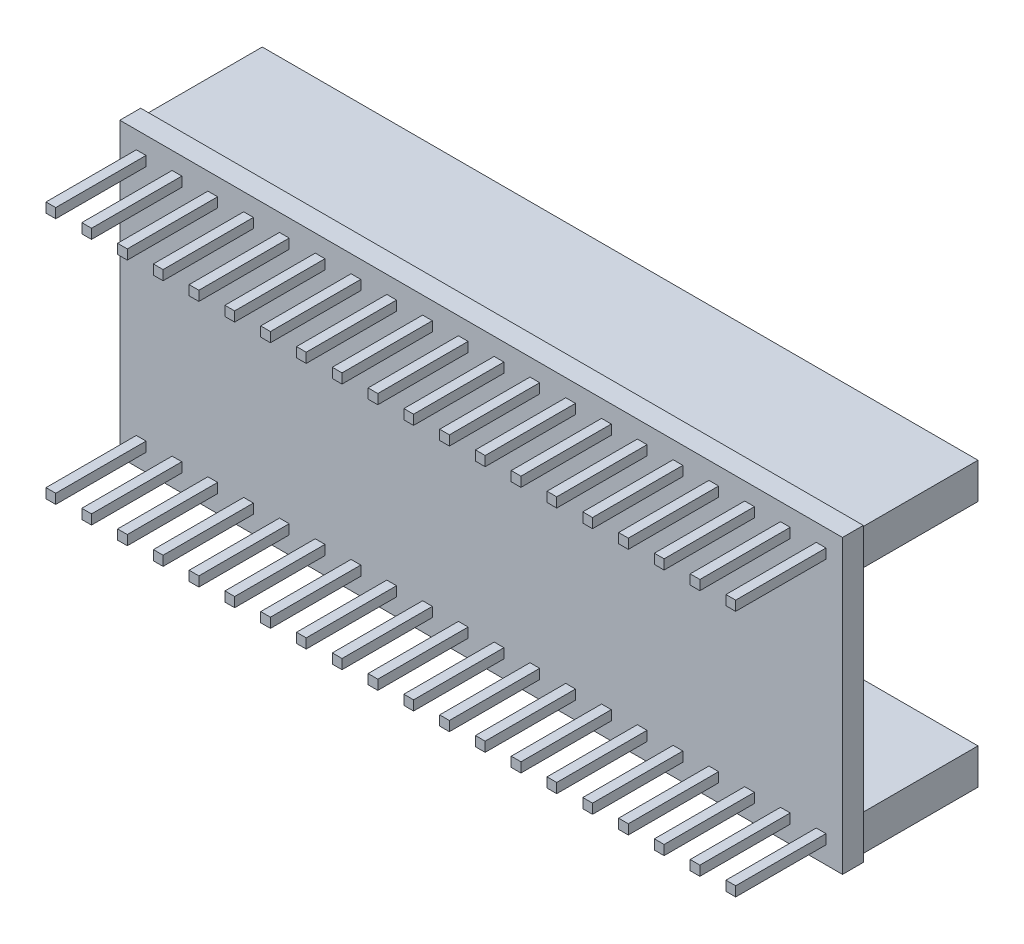
SolidWorks part; units mm, degrees
ref_plane "Спереди" through (0, 0, 0) normal (0, 0, 1) x (1, 0, 0)
ref_plane "Сверху" through (0, 0, 0) normal (0, 1, 0) x (1, 0, 0)
ref_plane "Справа" through (0, 0, 0) normal (1, 0, 0) x (0, 0, -1)
sketch "Эскиз1" plane through (0, 0, 0) normal (0, 0, 1) x (1, 0, 0)
  line L0 (-56.9339, 10.5) -> (3.8181, 10.5) construction
  line L1 (0, 0) -> (-52, 0)
  line L2 (0, 0) -> (0, 21)
  line L3 (0, 21) -> (-52, 21)
  line L4 (-52, 0) -> (-52, 21)
  line L5 (-26, 25.408) -> (-26, -2.6209) construction
  line L6 (-51.75, 18.1125) -> (-0.25, 18.1125)
  line L7 (-51.75, 18.1125) -> (-51.75, 20.6875)
  line L8 (-51.75, 20.6875) -> (-0.25, 20.6875)
  line L9 (-0.25, 18.1125) -> (-0.25, 20.6875)
  line L10 (-0.25, 2.8875) -> (-0.25, 0.3125)
  line L11 (-51.75, 0.3125) -> (-0.25, 0.3125)
  line L12 (-51.75, 2.8875) -> (-0.25, 2.8875)
  line L13 (-51.75, 2.8875) -> (-51.75, 0.3125)
  line L14 (-49.175, 20.6875) -> (-49.175, 18.1125) construction
  line L15 (-50.4625, 20.8345) -> (-50.4625, 17.8759) construction
  line L16 (-51.907, 19.4) -> (-48.9961, 19.4) construction
  line L17 (-48.2375, 19.05) -> (-48.2375, 19.75)
  line L18 (-50.8125, 19.05) -> (-50.1125, 19.05)
  line L19 (-50.8125, 19.05) -> (-50.8125, 19.75)
  line L20 (-50.8125, 19.75) -> (-50.1125, 19.75)
  line L21 (-50.1125, 19.05) -> (-50.1125, 19.75)
  line L22 (-50.8125, 19.05) -> (-50.1125, 19.75) construction
  line L23 (-50.8125, 19.75) -> (-50.1125, 19.05) construction
  line L24 (-48.2375, 19.05) -> (-47.5375, 19.05)
  line L25 (-47.5375, 19.05) -> (-47.5375, 19.75)
  line L26 (-48.2375, 19.75) -> (-47.5375, 19.75)
  line L27 (-48.2375, 19.75) -> (-47.5375, 19.05) construction
  line L28 (-48.2375, 19.05) -> (-47.5375, 19.75) construction
  line L29 (-45.6625, 19.05) -> (-45.6625, 19.75)
  line L30 (-45.6625, 19.05) -> (-44.9625, 19.05)
  line L31 (-44.9625, 19.05) -> (-44.9625, 19.75)
  line L32 (-45.6625, 19.75) -> (-44.9625, 19.75)
  line L33 (-45.6625, 19.75) -> (-44.9625, 19.05) construction
  line L34 (-45.6625, 19.05) -> (-44.9625, 19.75) construction
  line L35 (-43.0875, 19.05) -> (-43.0875, 19.75)
  line L36 (-43.0875, 19.05) -> (-42.3875, 19.05)
  line L37 (-42.3875, 19.05) -> (-42.3875, 19.75)
  line L38 (-43.0875, 19.75) -> (-42.3875, 19.75)
  line L39 (-43.0875, 19.75) -> (-42.3875, 19.05) construction
  line L40 (-43.0875, 19.05) -> (-42.3875, 19.75) construction
  line L41 (-40.5125, 19.05) -> (-40.5125, 19.75)
  line L42 (-40.5125, 19.05) -> (-39.8125, 19.05)
  line L43 (-39.8125, 19.05) -> (-39.8125, 19.75)
  line L44 (-40.5125, 19.75) -> (-39.8125, 19.75)
  line L45 (-40.5125, 19.75) -> (-39.8125, 19.05) construction
  line L46 (-40.5125, 19.05) -> (-39.8125, 19.75) construction
  line L47 (-37.9375, 19.05) -> (-37.9375, 19.75)
  line L48 (-37.9375, 19.05) -> (-37.2375, 19.05)
  line L49 (-37.2375, 19.05) -> (-37.2375, 19.75)
  line L50 (-37.9375, 19.75) -> (-37.2375, 19.75)
  line L51 (-37.9375, 19.75) -> (-37.2375, 19.05) construction
  line L52 (-37.9375, 19.05) -> (-37.2375, 19.75) construction
  line L53 (-35.3625, 19.05) -> (-35.3625, 19.75)
  line L54 (-35.3625, 19.05) -> (-34.6625, 19.05)
  line L55 (-34.6625, 19.05) -> (-34.6625, 19.75)
  line L56 (-35.3625, 19.75) -> (-34.6625, 19.75)
  line L57 (-35.3625, 19.75) -> (-34.6625, 19.05) construction
  line L58 (-35.3625, 19.05) -> (-34.6625, 19.75) construction
  line L59 (-32.7875, 19.05) -> (-32.7875, 19.75)
  line L60 (-32.7875, 19.05) -> (-32.0875, 19.05)
  line L61 (-32.0875, 19.05) -> (-32.0875, 19.75)
  line L62 (-32.7875, 19.75) -> (-32.0875, 19.75)
  line L63 (-32.7875, 19.75) -> (-32.0875, 19.05) construction
  line L64 (-32.7875, 19.05) -> (-32.0875, 19.75) construction
  line L65 (-30.2125, 19.05) -> (-30.2125, 19.75)
  line L66 (-30.2125, 19.05) -> (-29.5125, 19.05)
  line L67 (-29.5125, 19.05) -> (-29.5125, 19.75)
  line L68 (-30.2125, 19.75) -> (-29.5125, 19.75)
  line L69 (-30.2125, 19.75) -> (-29.5125, 19.05) construction
  line L70 (-30.2125, 19.05) -> (-29.5125, 19.75) construction
  line L71 (-27.6375, 19.05) -> (-27.6375, 19.75)
  line L72 (-27.6375, 19.05) -> (-26.9375, 19.05)
  line L73 (-26.9375, 19.05) -> (-26.9375, 19.75)
  line L74 (-27.6375, 19.75) -> (-26.9375, 19.75)
  line L75 (-27.6375, 19.75) -> (-26.9375, 19.05) construction
  line L76 (-27.6375, 19.05) -> (-26.9375, 19.75) construction
  line L77 (-25.0625, 19.05) -> (-25.0625, 19.75)
  line L78 (-25.0625, 19.05) -> (-24.3625, 19.05)
  line L79 (-24.3625, 19.05) -> (-24.3625, 19.75)
  line L80 (-25.0625, 19.75) -> (-24.3625, 19.75)
  line L81 (-25.0625, 19.75) -> (-24.3625, 19.05) construction
  line L82 (-25.0625, 19.05) -> (-24.3625, 19.75) construction
  line L83 (-22.4875, 19.05) -> (-22.4875, 19.75)
  line L84 (-22.4875, 19.05) -> (-21.7875, 19.05)
  line L85 (-21.7875, 19.05) -> (-21.7875, 19.75)
  line L86 (-22.4875, 19.75) -> (-21.7875, 19.75)
  line L87 (-22.4875, 19.75) -> (-21.7875, 19.05) construction
  line L88 (-22.4875, 19.05) -> (-21.7875, 19.75) construction
  line L89 (-19.9125, 19.05) -> (-19.9125, 19.75)
  line L90 (-19.9125, 19.05) -> (-19.2125, 19.05)
  line L91 (-19.2125, 19.05) -> (-19.2125, 19.75)
  line L92 (-19.9125, 19.75) -> (-19.2125, 19.75)
  line L93 (-19.9125, 19.75) -> (-19.2125, 19.05) construction
  line L94 (-19.9125, 19.05) -> (-19.2125, 19.75) construction
  line L95 (-17.3375, 19.05) -> (-17.3375, 19.75)
  line L96 (-17.3375, 19.05) -> (-16.6375, 19.05)
  line L97 (-16.6375, 19.05) -> (-16.6375, 19.75)
  line L98 (-17.3375, 19.75) -> (-16.6375, 19.75)
  line L99 (-17.3375, 19.75) -> (-16.6375, 19.05) construction
  line L100 (-17.3375, 19.05) -> (-16.6375, 19.75) construction
  line L101 (-14.7625, 19.05) -> (-14.7625, 19.75)
  line L102 (-14.7625, 19.05) -> (-14.0625, 19.05)
  line L103 (-14.0625, 19.05) -> (-14.0625, 19.75)
  line L104 (-14.7625, 19.75) -> (-14.0625, 19.75)
  line L105 (-14.7625, 19.75) -> (-14.0625, 19.05) construction
  line L106 (-14.7625, 19.05) -> (-14.0625, 19.75) construction
  line L107 (-12.1875, 19.05) -> (-12.1875, 19.75)
  line L108 (-12.1875, 19.05) -> (-11.4875, 19.05)
  line L109 (-11.4875, 19.05) -> (-11.4875, 19.75)
  line L110 (-12.1875, 19.75) -> (-11.4875, 19.75)
  line L111 (-12.1875, 19.75) -> (-11.4875, 19.05) construction
  line L112 (-12.1875, 19.05) -> (-11.4875, 19.75) construction
  line L113 (-9.6125, 19.05) -> (-9.6125, 19.75)
  line L114 (-9.6125, 19.05) -> (-8.9125, 19.05)
  line L115 (-8.9125, 19.05) -> (-8.9125, 19.75)
  line L116 (-9.6125, 19.75) -> (-8.9125, 19.75)
  line L117 (-9.6125, 19.75) -> (-8.9125, 19.05) construction
  line L118 (-9.6125, 19.05) -> (-8.9125, 19.75) construction
  line L119 (-7.0375, 19.05) -> (-7.0375, 19.75)
  line L120 (-7.0375, 19.05) -> (-6.3375, 19.05)
  line L121 (-6.3375, 19.05) -> (-6.3375, 19.75)
  line L122 (-7.0375, 19.75) -> (-6.3375, 19.75)
  line L123 (-7.0375, 19.75) -> (-6.3375, 19.05) construction
  line L124 (-7.0375, 19.05) -> (-6.3375, 19.75) construction
  line L125 (-4.4625, 19.05) -> (-4.4625, 19.75)
  line L126 (-4.4625, 19.05) -> (-3.7625, 19.05)
  line L127 (-3.7625, 19.05) -> (-3.7625, 19.75)
  line L128 (-4.4625, 19.75) -> (-3.7625, 19.75)
  line L129 (-4.4625, 19.75) -> (-3.7625, 19.05) construction
  line L130 (-4.4625, 19.05) -> (-3.7625, 19.75) construction
  line L131 (-1.8875, 19.05) -> (-1.8875, 19.75)
  line L132 (-1.8875, 19.05) -> (-1.1875, 19.05)
  line L133 (-1.1875, 19.05) -> (-1.1875, 19.75)
  line L134 (-1.8875, 19.75) -> (-1.1875, 19.75)
  line L135 (-1.8875, 19.75) -> (-1.1875, 19.05) construction
  line L136 (-1.8875, 19.05) -> (-1.1875, 19.75) construction
  line L137 (-50.8125, 1.95) -> (-50.1125, 1.25) construction
  line L138 (-50.8125, 1.25) -> (-50.1125, 1.95) construction
  line L139 (-50.8125, 1.25) -> (-50.1125, 1.25)
  line L140 (-50.1125, 1.95) -> (-50.1125, 1.25)
  line L141 (-50.8125, 1.95) -> (-50.1125, 1.95)
  line L142 (-50.8125, 1.95) -> (-50.8125, 1.25)
  line L143 (-48.2375, 1.25) -> (-47.5375, 1.25)
  line L144 (-47.5375, 1.95) -> (-47.5375, 1.25)
  line L145 (-48.2375, 1.95) -> (-47.5375, 1.95)
  line L146 (-48.2375, 1.95) -> (-48.2375, 1.25)
  line L147 (-48.2375, 1.95) -> (-47.5375, 1.25) construction
  line L148 (-48.2375, 1.25) -> (-47.5375, 1.95) construction
  line L149 (-45.6625, 1.25) -> (-44.9625, 1.25)
  line L150 (-44.9625, 1.95) -> (-44.9625, 1.25)
  line L151 (-45.6625, 1.95) -> (-44.9625, 1.95)
  line L152 (-45.6625, 1.95) -> (-45.6625, 1.25)
  line L153 (-45.6625, 1.95) -> (-44.9625, 1.25) construction
  line L154 (-45.6625, 1.25) -> (-44.9625, 1.95) construction
  line L155 (-43.0875, 1.25) -> (-42.3875, 1.25)
  line L156 (-42.3875, 1.95) -> (-42.3875, 1.25)
  line L157 (-43.0875, 1.95) -> (-42.3875, 1.95)
  line L158 (-43.0875, 1.95) -> (-43.0875, 1.25)
  line L159 (-43.0875, 1.95) -> (-42.3875, 1.25) construction
  line L160 (-43.0875, 1.25) -> (-42.3875, 1.95) construction
  line L161 (-40.5125, 1.25) -> (-39.8125, 1.25)
  line L162 (-39.8125, 1.95) -> (-39.8125, 1.25)
  line L163 (-40.5125, 1.95) -> (-39.8125, 1.95)
  line L164 (-40.5125, 1.95) -> (-40.5125, 1.25)
  line L165 (-40.5125, 1.95) -> (-39.8125, 1.25) construction
  line L166 (-40.5125, 1.25) -> (-39.8125, 1.95) construction
  line L167 (-37.9375, 1.25) -> (-37.2375, 1.25)
  line L168 (-37.2375, 1.95) -> (-37.2375, 1.25)
  line L169 (-37.9375, 1.95) -> (-37.2375, 1.95)
  line L170 (-37.9375, 1.95) -> (-37.9375, 1.25)
  line L171 (-37.9375, 1.95) -> (-37.2375, 1.25) construction
  line L172 (-37.9375, 1.25) -> (-37.2375, 1.95) construction
  line L173 (-35.3625, 1.25) -> (-34.6625, 1.25)
  line L174 (-34.6625, 1.95) -> (-34.6625, 1.25)
  line L175 (-35.3625, 1.95) -> (-34.6625, 1.95)
  line L176 (-35.3625, 1.95) -> (-35.3625, 1.25)
  line L177 (-35.3625, 1.95) -> (-34.6625, 1.25) construction
  line L178 (-35.3625, 1.25) -> (-34.6625, 1.95) construction
  line L179 (-32.7875, 1.25) -> (-32.0875, 1.25)
  line L180 (-32.0875, 1.95) -> (-32.0875, 1.25)
  line L181 (-32.7875, 1.95) -> (-32.0875, 1.95)
  line L182 (-32.7875, 1.95) -> (-32.7875, 1.25)
  line L183 (-32.7875, 1.95) -> (-32.0875, 1.25) construction
  line L184 (-32.7875, 1.25) -> (-32.0875, 1.95) construction
  line L185 (-30.2125, 1.25) -> (-29.5125, 1.25)
  line L186 (-29.5125, 1.95) -> (-29.5125, 1.25)
  line L187 (-30.2125, 1.95) -> (-29.5125, 1.95)
  line L188 (-30.2125, 1.95) -> (-30.2125, 1.25)
  line L189 (-30.2125, 1.95) -> (-29.5125, 1.25) construction
  line L190 (-30.2125, 1.25) -> (-29.5125, 1.95) construction
  line L191 (-27.6375, 1.25) -> (-26.9375, 1.25)
  line L192 (-26.9375, 1.95) -> (-26.9375, 1.25)
  line L193 (-27.6375, 1.95) -> (-26.9375, 1.95)
  line L194 (-27.6375, 1.95) -> (-27.6375, 1.25)
  line L195 (-27.6375, 1.95) -> (-26.9375, 1.25) construction
  line L196 (-27.6375, 1.25) -> (-26.9375, 1.95) construction
  line L197 (-25.0625, 1.25) -> (-24.3625, 1.25)
  line L198 (-24.3625, 1.95) -> (-24.3625, 1.25)
  line L199 (-25.0625, 1.95) -> (-24.3625, 1.95)
  line L200 (-25.0625, 1.95) -> (-25.0625, 1.25)
  line L201 (-25.0625, 1.95) -> (-24.3625, 1.25) construction
  line L202 (-25.0625, 1.25) -> (-24.3625, 1.95) construction
  line L203 (-22.4875, 1.25) -> (-21.7875, 1.25)
  line L204 (-21.7875, 1.95) -> (-21.7875, 1.25)
  line L205 (-22.4875, 1.95) -> (-21.7875, 1.95)
  line L206 (-22.4875, 1.95) -> (-22.4875, 1.25)
  line L207 (-22.4875, 1.95) -> (-21.7875, 1.25) construction
  line L208 (-22.4875, 1.25) -> (-21.7875, 1.95) construction
  line L209 (-19.9125, 1.25) -> (-19.2125, 1.25)
  line L210 (-19.2125, 1.95) -> (-19.2125, 1.25)
  line L211 (-19.9125, 1.95) -> (-19.2125, 1.95)
  line L212 (-19.9125, 1.95) -> (-19.9125, 1.25)
  line L213 (-19.9125, 1.95) -> (-19.2125, 1.25) construction
  line L214 (-19.9125, 1.25) -> (-19.2125, 1.95) construction
  line L215 (-17.3375, 1.25) -> (-16.6375, 1.25)
  line L216 (-16.6375, 1.95) -> (-16.6375, 1.25)
  line L217 (-17.3375, 1.95) -> (-16.6375, 1.95)
  line L218 (-17.3375, 1.95) -> (-17.3375, 1.25)
  line L219 (-17.3375, 1.95) -> (-16.6375, 1.25) construction
  line L220 (-17.3375, 1.25) -> (-16.6375, 1.95) construction
  line L221 (-14.7625, 1.25) -> (-14.0625, 1.25)
  line L222 (-14.0625, 1.95) -> (-14.0625, 1.25)
  line L223 (-14.7625, 1.95) -> (-14.0625, 1.95)
  line L224 (-14.7625, 1.95) -> (-14.7625, 1.25)
  line L225 (-14.7625, 1.95) -> (-14.0625, 1.25) construction
  line L226 (-14.7625, 1.25) -> (-14.0625, 1.95) construction
  line L227 (-12.1875, 1.25) -> (-11.4875, 1.25)
  line L228 (-11.4875, 1.95) -> (-11.4875, 1.25)
  line L229 (-12.1875, 1.95) -> (-11.4875, 1.95)
  line L230 (-12.1875, 1.95) -> (-12.1875, 1.25)
  line L231 (-12.1875, 1.95) -> (-11.4875, 1.25) construction
  line L232 (-12.1875, 1.25) -> (-11.4875, 1.95) construction
  line L233 (-9.6125, 1.25) -> (-8.9125, 1.25)
  line L234 (-8.9125, 1.95) -> (-8.9125, 1.25)
  line L235 (-9.6125, 1.95) -> (-8.9125, 1.95)
  line L236 (-9.6125, 1.95) -> (-9.6125, 1.25)
  line L237 (-9.6125, 1.95) -> (-8.9125, 1.25) construction
  line L238 (-9.6125, 1.25) -> (-8.9125, 1.95) construction
  line L239 (-7.0375, 1.25) -> (-6.3375, 1.25)
  line L240 (-6.3375, 1.95) -> (-6.3375, 1.25)
  line L241 (-7.0375, 1.95) -> (-6.3375, 1.95)
  line L242 (-7.0375, 1.95) -> (-7.0375, 1.25)
  line L243 (-7.0375, 1.95) -> (-6.3375, 1.25) construction
  line L244 (-7.0375, 1.25) -> (-6.3375, 1.95) construction
  line L245 (-4.4625, 1.25) -> (-3.7625, 1.25)
  line L246 (-3.7625, 1.95) -> (-3.7625, 1.25)
  line L247 (-4.4625, 1.95) -> (-3.7625, 1.95)
  line L248 (-4.4625, 1.95) -> (-4.4625, 1.25)
  line L249 (-4.4625, 1.95) -> (-3.7625, 1.25) construction
  line L250 (-4.4625, 1.25) -> (-3.7625, 1.95) construction
  line L251 (-1.8875, 1.25) -> (-1.1875, 1.25)
  line L252 (-1.1875, 1.95) -> (-1.1875, 1.25)
  line L253 (-1.8875, 1.95) -> (-1.1875, 1.95)
  line L254 (-1.8875, 1.95) -> (-1.8875, 1.25)
  line L255 (-1.8875, 1.95) -> (-1.1875, 1.25) construction
  line L256 (-1.8875, 1.25) -> (-1.1875, 1.95) construction
  point P7 (-52, 10.5)
  point P14 (-26, 21)
  point P15 (-26, 18.1125)
  point P20 (-51.75, 19.4)
  point P21 (-51.75, 1.6)
  point P28 (-49.175, 19.4)
  point P29 (-50.4625, 19.4)
  point P34 (-47.8875, 19.4)
  point P115 (-50.4625, 1.6)
  point P116 (-47.8875, 1.6)
  dimension "D1" = 21
  dimension "D2" = 52
  dimension "D3" = 51.5
  dimension "D4" = 17.8
  dimension "D5" = 2.575
  dimension "D6" = 2.575
  dimension "D7" = 0.7
  dimension "D9" = 2.575
  dimension "D11" = 2.575
  dimension "D8" = 20
  dimension "D10" = 20
extrude "Бобышка-Вытянуть1" add sketch "Эскиз1" along normal blind 1.5 contours L4 L1 L2 L3 L13 L12 L10 L11 L9 L6 L7 L8 | L6 L9 L8 L7 L21 L18 L19 L20 L17 L26 L25 L24 L29 L32 L31 L30 L35 L38 L37 L36 L41 L44 L43 L42 L47 L50 L49 L48 L53 L56 L55 L54 L59 L62 L61 L60 L65 L68 L67 L66 L71 | L12 L13 L11 L10 L254 L253 L252 L251 L248 L247 L246 L245 L242 L241 L240 L239 L236 L235 L234 L233 L230 L229 L228 L227 L224 L223 L222 L221 L218 L217 L216 L215 L212 L211 L210 L209 L206 L205 L204 L203 L200 region at (-26, 10.5, 0) region at (-26, 19.4, 0) region at (-26, 1.6, 0)
sketch "Эскиз2" plane through (0, 0, 0) normal (0, 0, -1) x (-1, 0, 0)
extrude "Бобышка-Вытянуть2" add sketch "Эскиз1<4>" against normal blind 8.5 contours L6 L9 L8 L7 L21 L18 L19 L20 L17 L26 L25 L24 L29 L32 L31 L30 L35 L38 L37 L36 L41 L44 L43 L42 L47 L50 L49 L48 L53 L56 L55 L54 L59 L62 L61 L60 L65 L68 L67 L66 L71 | L12 L13 L11 L10 L254 L253 L252 L251 L248 L247 L246 L245 L242 L241 L240 L239 L236 L235 L234 L233 L230 L229 L228 L227 L224 L223 L222 L221 L218 L217 L216 L215 L212 L211 L210 L209 L206 L205 L204 L203 L200 region at (-26, 19.4, 0) region at (-26, 1.6, 0)
sketch "Эскиз1<4>" plane through (0, 0, 0) normal (0, 0, 1) x (1, 0, 0) same geometry as "Эскиз1"
extrude "Бобышка-Вытянуть3" add sketch "Эскиз1<5>" along normal blind 8 contours L18 L21 L20 L19 | L26 L17 L24 L25 | L32 L29 L30 L31 | L36 L37 L38 L35 | L42 L43 L44 L41 | L48 L49 L50 L47 | L54 L55 L56 L53 | L60 L61 L62 L59 | L66 L67 L68 L65 | L72 L73 L74 L71 | L78 L79 L80 L77 | L84 L85 L86 L83 | L90 L91 L92 L89 | L96 L97 L98 L95 | L102 L103 L104 L101 | L108 L109 L110 L107 | L114 L115 L116 L113 | L120 L121 L122 L119 | L126 L127 L128 L125 | L132 L133 L134 L131 | L251 L252 L253 L254 | L245 L246 L247 L248 | L239 L240 L241 L242 | L233 L234 L235 L236 | L227 L228 L229 L230 | L221 L222 L223 L224 | L215 L216 L217 L218 | L209 L210 L211 L212 | L203 L204 L205 L206 | L197 L198 L199 L200 | L191 L192 L193 L194 | L185 L186 L187 L188 | L179 L180 L181 L182 | L173 L174 L175 L176 | L167 L168 L169 L170 | L161 L162 L163 L164 | L155 L156 L157 L158 | L149 L150 L151 L152 | L143 L144 L145 L146 | L139 L140 L141 L142 region at (-47.8875, 19.4, 0) region at (-50.4625, 19.4, 0) region at (-45.3125, 19.4, 0)
sketch "Эскиз1<5>" plane through (0, 0, 0) normal (0, 0, 1) x (1, 0, 0) same geometry as "Эскиз1"
